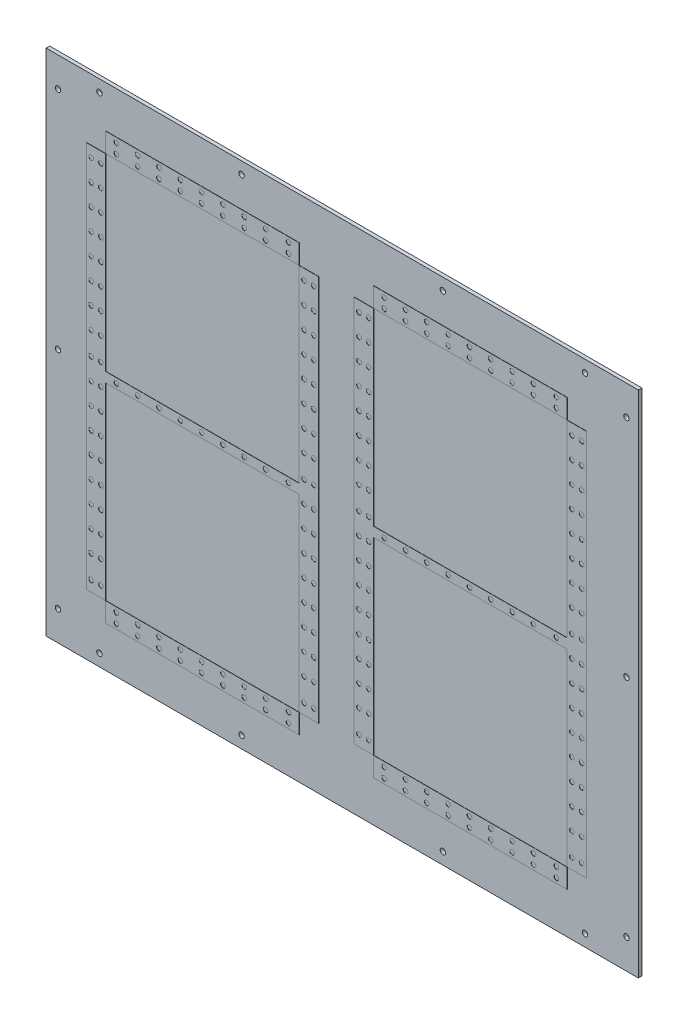
SolidWorks part; units mm, degrees
material "AISI 1020"
ref_plane "Front Plane" through (0, 0, 0) normal (0, 0, 1) x (1, 0, 0)
ref_plane "Top Plane" through (0, 0, 0) normal (0, 1, 0) x (1, 0, 0)
ref_plane "Right Plane" through (0, 0, 0) normal (1, 0, 0) x (0, 0, -1)
other "Caixa delimitadora"
ref_plane "Default Plane" through (-275, -250, -3) normal (0, 1, 0) x (1, 0, 0)
sketch "Esboço3" plane through (0, 0, 0) normal (0, 0, 1) x (1, 0, 0)
  line L0 (19.423, -163.6696) -> (49.423, -163.6696) construction
  line L2 (34.423, -163.6696) -> (34.423, -0.5317) construction
  line L5 (-0.277, -0.3121) -> (-0.277, 22.0323) construction
  line B0 (3.023, -171.9902) -> (-160.3346, -171.9902)
  line B1 (3.023, -4.4121) -> (-160.3346, -4.4121)
  line B2 (3.023, -0.3121) -> (3.023, 163.0455)
  line B3 (3.023, 3.7879) -> (-160.3346, 3.7879)
  line B4 (3.0164, 171.3782) -> (-160.3411, 171.3782)
  line B5 (11.223, -0.3121) -> (11.223, 163.0455)
  line B6 (3.023, -163.7902) -> (-160.3346, -163.7902)
  line B7 (3.0164, 163.1782) -> (-160.3411, 163.1782)
  line B8 (3.0164, 167.2782) -> (-160.3411, 167.2782) construction
  circle B9 centre (-5.9836, 167.2782) radius 2
  line B10 (3.0164, 163.1782) -> (3.0164, 171.3782)
  circle B11 centre (-43.3411, 167.2782) radius 2
  circle B12 centre (-151.3411, 167.2782) radius 2
  line B13 (-160.3411, 163.1782) -> (-160.3411, 171.3782)
  circle B14 centre (-61.3411, 167.2782) radius 2
  circle B15 centre (-25.3411, 167.2782) radius 2
  circle B16 centre (-79.3411, 167.2782) radius 2
  circle B17 centre (-97.3411, 167.2782) radius 2
  circle B18 centre (-115.3411, 167.2782) radius 2
  circle B19 centre (-133.3411, 167.2782) radius 2
  circle B20 centre (7.123, 154.0455) radius 2
  circle B21 centre (-5.977, -167.8902) radius 2
  line B22 (-160.3346, -171.9902) -> (-160.3346, -163.7902)
  line B23 (3.023, -171.9902) -> (3.023, -163.7902)
  circle B24 centre (-25.3346, -167.8902) radius 2
  circle B25 centre (-43.3346, -167.8902) radius 2
  circle B26 centre (-61.3346, -167.8902) radius 2
  circle B27 centre (-79.3346, -167.8902) radius 2
  circle B28 centre (-97.3346, -167.8902) radius 2
  circle B29 centre (-115.3346, -167.8902) radius 2
  circle B30 centre (-133.3346, -167.8902) radius 2
  circle B31 centre (-151.3346, -167.8902) radius 2
  circle B32 centre (-5.977, -0.3121) radius 2
  line B33 (-160.3346, -4.4121) -> (-160.3346, 3.7879)
  line B34 (3.023, -4.4121) -> (3.023, 3.7879)
  circle B35 centre (-25.3346, -0.3121) radius 2
  circle B36 centre (-43.3346, -0.3121) radius 2
  circle B37 centre (-61.3346, -0.3121) radius 2
  circle B38 centre (-79.3346, -0.3121) radius 2
  circle B39 centre (-97.3346, -0.3121) radius 2
  circle B40 centre (-115.3346, -0.3121) radius 2
  circle B41 centre (-133.3346, -0.3121) radius 2
  circle B42 centre (-151.3346, -0.3121) radius 2
  circle B43 centre (7.123, 8.6879) radius 2
  line B44 (3.023, 163.0455) -> (11.223, 163.0455)
  line B45 (3.023, -0.3121) -> (11.223, -0.3121)
  circle B46 centre (7.123, 28.0455) radius 2
  circle B47 centre (7.123, 46.0455) radius 2
  circle B48 centre (7.123, 64.0455) radius 2
  circle B49 centre (7.123, 82.0455) radius 2
  circle B50 centre (7.123, 100.0455) radius 2
  circle B51 centre (7.123, 118.0455) radius 2
  circle B52 centre (7.123, 136.0455) radius 2
  line B53 (3.023, -176.0902) -> (-160.3346, -176.0902) construction
  line B54 (3.023, -180.1902) -> (-160.3346, -180.1902)
  line B55 (3.023, -180.1902) -> (3.023, -171.9902)
  line B56 (3.023, -171.9902) -> (-160.3346, -171.9902)
  line B57 (-160.3346, -180.1902) -> (-160.3346, -171.9902)
  circle B58 centre (-5.977, -176.0902) radius 2
  circle B59 centre (-25.3346, -176.0902) radius 2
  circle B60 centre (-43.3346, -176.0902) radius 2
  circle B61 centre (-61.3346, -176.0902) radius 2
  circle B62 centre (-79.3346, -176.0902) radius 2
  circle B63 centre (-97.3346, -176.0902) radius 2
  circle B64 centre (-115.3346, -176.0902) radius 2
  circle B65 centre (-133.3346, -176.0902) radius 2
  circle B66 centre (-151.3346, -176.0902) radius 2
  line B67 (3.0164, 175.4782) -> (-160.3411, 175.4782) construction
  line B68 (3.0164, 171.3782) -> (-160.3411, 171.3782)
  line B69 (3.0164, 171.3782) -> (3.0164, 179.5782)
  line B70 (3.0164, 179.5782) -> (-160.3411, 179.5782)
  line B71 (-160.3411, 171.3782) -> (-160.3411, 179.5782)
  circle B72 centre (-5.9836, 175.4782) radius 2
  circle B73 centre (-25.3411, 175.4782) radius 2
  circle B74 centre (-43.3411, 175.4782) radius 2
  circle B75 centre (-61.3411, 175.4782) radius 2
  circle B76 centre (-79.3411, 175.4782) radius 2
  circle B77 centre (-97.3411, 175.4782) radius 2
  circle B78 centre (-115.3411, 175.4782) radius 2
  circle B79 centre (-133.3411, 175.4782) radius 2
  circle B80 centre (-151.3411, 175.4782) radius 2
  line B81 (11.223, -163.6696) -> (11.223, -0.3121)
  line B82 (3.023, -163.6696) -> (3.023, -0.3121)
  line B83 (7.123, -163.6696) -> (7.123, -0.3121) construction
  line B84 (3.023, -163.6696) -> (11.223, -163.6696)
  line B85 (3.023, -0.3121) -> (11.223, -0.3121)
  circle B86 centre (7.123, -154.6696) radius 2
  circle B87 centre (7.123, -135.3121) radius 2
  circle B88 centre (7.123, -117.3121) radius 2
  circle B89 centre (7.123, -99.3121) radius 2
  circle B90 centre (7.123, -81.3121) radius 2
  circle B91 centre (7.123, -63.3121) radius 2
  circle B92 centre (7.123, -45.3121) radius 2
  circle B93 centre (7.123, -27.3121) radius 2
  circle B94 centre (7.123, -9.3121) radius 2
  line B95 (-164.4346, -163.6696) -> (-164.4346, -0.3121) construction
  line B96 (-168.5346, -163.6696) -> (-168.5346, -0.3121)
  line B97 (-168.5346, -163.6696) -> (-160.3346, -163.6696)
  line B98 (-160.3346, -163.6696) -> (-160.3346, -0.3121)
  line B99 (-168.5346, -0.3121) -> (-160.3346, -0.3121)
  circle B100 centre (-164.4346, -154.6696) radius 2
  circle B101 centre (-164.4346, -135.3121) radius 2
  circle B102 centre (-164.4346, -117.3121) radius 2
  circle B103 centre (-164.4346, -99.3121) radius 2
  circle B104 centre (-164.4346, -81.3121) radius 2
  circle B105 centre (-164.4346, -63.3121) radius 2
  circle B106 centre (-164.4346, -45.3121) radius 2
  circle B107 centre (-164.4346, -27.3121) radius 2
  circle B108 centre (-164.4346, -9.3121) radius 2
  line B109 (-164.4346, -0.3121) -> (-164.4346, 163.0455) construction
  line B110 (-168.5346, -0.3121) -> (-168.5346, 163.0455)
  line B111 (-168.5346, -0.3121) -> (-160.3346, -0.3121)
  line B112 (-160.3346, -0.3121) -> (-160.3346, 163.0455)
  line B113 (-168.5346, 163.0455) -> (-160.3346, 163.0455)
  circle B114 centre (-164.4346, 8.6879) radius 2
  circle B115 centre (-164.4346, 28.0455) radius 2
  circle B116 centre (-164.4346, 46.0455) radius 2
  circle B117 centre (-164.4346, 64.0455) radius 2
  circle B118 centre (-164.4346, 82.0455) radius 2
  circle B119 centre (-164.4346, 100.0455) radius 2
  circle B120 centre (-164.4346, 118.0455) radius 2
  circle B121 centre (-164.4346, 136.0455) radius 2
  circle B122 centre (-164.4346, 154.0455) radius 2
  line B123 (15.323, -163.6696) -> (15.323, -0.3121) construction
  line B124 (11.223, -163.6696) -> (11.223, -0.3121)
  line B125 (11.223, -163.6696) -> (19.423, -163.6696)
  line B126 (19.423, -163.6696) -> (19.423, -0.3121)
  line B127 (11.223, -0.3121) -> (19.423, -0.3121)
  circle B128 centre (15.323, -154.6696) radius 2
  circle B129 centre (15.323, -135.3121) radius 2
  circle B130 centre (15.323, -117.3121) radius 2
  circle B131 centre (15.323, -99.3121) radius 2
  circle B132 centre (15.323, -81.3121) radius 2
  circle B133 centre (15.323, -63.3121) radius 2
  circle B134 centre (15.323, -45.3121) radius 2
  circle B135 centre (15.323, -27.3121) radius 2
  circle B136 centre (15.323, -9.3121) radius 2
  line B137 (11.223, -0.3121) -> (11.223, 163.0455)
  line B138 (11.223, -0.3121) -> (19.423, -0.3121)
  line B139 (19.423, -0.3121) -> (19.423, 163.0455)
  line B140 (11.223, 163.0455) -> (19.423, 163.0455)
  circle B141 centre (15.323, 8.6879) radius 2
  circle B142 centre (15.323, 28.0455) radius 2
  circle B143 centre (15.323, 46.0455) radius 2
  circle B144 centre (15.323, 64.0455) radius 2
  circle B145 centre (15.323, 82.0455) radius 2
  circle B146 centre (15.323, 100.0455) radius 2
  circle B147 centre (15.323, 118.0455) radius 2
  circle B148 centre (15.323, 136.0455) radius 2
  circle B149 centre (15.323, 154.0455) radius 2
  line B150 (-172.6346, -163.6696) -> (-172.6346, -0.3121) construction
  line B151 (-176.7346, -163.6696) -> (-176.7346, -0.3121)
  line B152 (-176.7346, -163.6696) -> (-168.5346, -163.6696)
  line B153 (-168.5346, -163.6696) -> (-168.5346, -0.3121)
  line B154 (-176.7346, -0.3121) -> (-168.5346, -0.3121)
  circle B155 centre (-172.6346, -154.6696) radius 2
  circle B156 centre (-172.6346, -135.3121) radius 2
  circle B157 centre (-172.6346, -117.3121) radius 2
  circle B158 centre (-172.6346, -99.3121) radius 2
  circle B159 centre (-172.6346, -81.3121) radius 2
  circle B160 centre (-172.6346, -63.3121) radius 2
  circle B161 centre (-172.6346, -45.3121) radius 2
  circle B162 centre (-172.6346, -27.3121) radius 2
  circle B163 centre (-172.6346, -9.3121) radius 2
  line B164 (-172.6346, -0.3121) -> (-172.6346, 163.0455) construction
  line B165 (-176.7346, -0.3121) -> (-176.7346, 163.0455)
  line B166 (-176.7346, -0.3121) -> (-168.5346, -0.3121)
  line B167 (-168.5346, -0.3121) -> (-168.5346, 163.0455)
  line B168 (-176.7346, 163.0455) -> (-168.5346, 163.0455)
  circle B169 centre (-172.6346, 8.6879) radius 2
  circle B170 centre (-172.6346, 28.0455) radius 2
  circle B171 centre (-172.6346, 46.0455) radius 2
  circle B172 centre (-172.6346, 64.0455) radius 2
  circle B173 centre (-172.6346, 82.0455) radius 2
  circle B174 centre (-172.6346, 100.0455) radius 2
  circle B175 centre (-172.6346, 118.0455) radius 2
  circle B176 centre (-172.6346, 136.0455) radius 2
  circle B177 centre (-172.6346, 154.0455) radius 2
  line B178 (229.1805, -171.9902) -> (65.823, -171.9902)
  line B179 (229.1805, -4.4121) -> (65.823, -4.4121)
  line B180 (229.1805, -0.3121) -> (229.1805, 163.0455)
  line B181 (229.1805, 3.7879) -> (65.823, 3.7879)
  line B182 (229.174, 171.3782) -> (65.8164, 171.3782)
  line B183 (237.3805, -0.3121) -> (237.3805, 163.0455)
  line B184 (229.1805, -163.7902) -> (65.823, -163.7902)
  line B185 (229.174, 163.1782) -> (65.8164, 163.1782)
  line B186 (229.174, 167.2782) -> (65.8164, 167.2782) construction
  circle B187 centre (220.174, 167.2782) radius 2
  line B188 (229.174, 163.1782) -> (229.174, 171.3782)
  circle B189 centre (182.8164, 167.2782) radius 2
  circle B190 centre (74.8164, 167.2782) radius 2
  line B191 (65.8164, 163.1782) -> (65.8164, 171.3782)
  circle B192 centre (164.8164, 167.2782) radius 2
  circle B193 centre (200.8164, 167.2782) radius 2
  circle B194 centre (146.8164, 167.2782) radius 2
  circle B195 centre (128.8164, 167.2782) radius 2
  circle B196 centre (110.8164, 167.2782) radius 2
  circle B197 centre (92.8164, 167.2782) radius 2
  circle B198 centre (233.2805, 154.0455) radius 2
  circle B199 centre (220.1805, -167.8902) radius 2
  line B200 (65.823, -171.9902) -> (65.823, -163.7902)
  line B201 (229.1805, -171.9902) -> (229.1805, -163.7902)
  circle B202 centre (200.823, -167.8902) radius 2
  circle B203 centre (182.823, -167.8902) radius 2
  circle B204 centre (164.823, -167.8902) radius 2
  circle B205 centre (146.823, -167.8902) radius 2
  circle B206 centre (128.823, -167.8902) radius 2
  circle B207 centre (110.823, -167.8902) radius 2
  circle B208 centre (92.823, -167.8902) radius 2
  circle B209 centre (74.823, -167.8902) radius 2
  circle B210 centre (220.1805, -0.3121) radius 2
  line B211 (65.823, -4.4121) -> (65.823, 3.7879)
  line B212 (229.1805, -4.4121) -> (229.1805, 3.7879)
  circle B213 centre (200.823, -0.3121) radius 2
  circle B214 centre (182.823, -0.3121) radius 2
  circle B215 centre (164.823, -0.3121) radius 2
  circle B216 centre (146.823, -0.3121) radius 2
  circle B217 centre (128.823, -0.3121) radius 2
  circle B218 centre (110.823, -0.3121) radius 2
  circle B219 centre (92.823, -0.3121) radius 2
  circle B220 centre (74.823, -0.3121) radius 2
  circle B221 centre (233.2805, 8.6879) radius 2
  line B222 (229.1805, 163.0455) -> (237.3805, 163.0455)
  line B223 (229.1805, -0.3121) -> (237.3805, -0.3121)
  circle B224 centre (233.2805, 28.0455) radius 2
  circle B225 centre (233.2805, 46.0455) radius 2
  circle B226 centre (233.2805, 64.0455) radius 2
  circle B227 centre (233.2805, 82.0455) radius 2
  circle B228 centre (233.2805, 100.0455) radius 2
  circle B229 centre (233.2805, 118.0455) radius 2
  circle B230 centre (233.2805, 136.0455) radius 2
  line B231 (229.1805, -0.3121) -> (65.823, -0.3121) construction
  line B232 (233.2805, -0.3121) -> (233.2805, 163.0455) construction
  line B233 (229.1805, -180.1902) -> (65.823, -180.1902)
  line B234 (229.1805, -180.1902) -> (229.1805, -171.9902)
  line B235 (229.1805, -171.9902) -> (65.823, -171.9902)
  line B236 (65.823, -180.1902) -> (65.823, -171.9902)
  circle B237 centre (220.1805, -176.0902) radius 2
  circle B238 centre (200.823, -176.0902) radius 2
  circle B239 centre (182.823, -176.0902) radius 2
  circle B240 centre (164.823, -176.0902) radius 2
  circle B241 centre (146.823, -176.0902) radius 2
  circle B242 centre (128.823, -176.0902) radius 2
  circle B243 centre (110.823, -176.0902) radius 2
  circle B244 centre (92.823, -176.0902) radius 2
  circle B245 centre (74.823, -176.0902) radius 2
  line B246 (229.174, 175.4782) -> (65.8164, 175.4782) construction
  line B247 (229.174, 171.3782) -> (65.8164, 171.3782)
  line B248 (229.174, 171.3782) -> (229.174, 179.5782)
  line B249 (229.174, 179.5782) -> (65.8164, 179.5782)
  line B250 (65.8164, 171.3782) -> (65.8164, 179.5782)
  circle B251 centre (220.174, 175.4782) radius 2
  circle B252 centre (200.8164, 175.4782) radius 2
  circle B253 centre (182.8164, 175.4782) radius 2
  circle B254 centre (164.8164, 175.4782) radius 2
  circle B255 centre (146.8164, 175.4782) radius 2
  circle B256 centre (128.8164, 175.4782) radius 2
  circle B257 centre (110.8164, 175.4782) radius 2
  circle B258 centre (92.8164, 175.4782) radius 2
  circle B259 centre (74.8164, 175.4782) radius 2
  line B260 (237.3805, -163.6696) -> (237.3805, -0.3121)
  line B261 (229.1805, -163.6696) -> (229.1805, -0.3121)
  line B262 (233.2805, -163.6696) -> (233.2805, -0.3121) construction
  line B263 (229.1805, -163.6696) -> (237.3805, -163.6696)
  line B264 (229.1805, -0.3121) -> (237.3805, -0.3121)
  circle B265 centre (233.2805, -154.6696) radius 2
  circle B266 centre (233.2805, -135.3121) radius 2
  circle B267 centre (233.2805, -117.3121) radius 2
  circle B268 centre (233.2805, -99.3121) radius 2
  circle B269 centre (233.2805, -81.3121) radius 2
  circle B270 centre (233.2805, -63.3121) radius 2
  circle B271 centre (233.2805, -45.3121) radius 2
  circle B272 centre (233.2805, -27.3121) radius 2
  circle B273 centre (233.2805, -9.3121) radius 2
  line B274 (57.623, -163.6696) -> (57.623, -0.3121)
  line B275 (57.623, -163.6696) -> (65.823, -163.6696)
  line B276 (65.823, -163.6696) -> (65.823, -0.3121)
  line B277 (57.623, -0.3121) -> (65.823, -0.3121)
  circle B278 centre (61.723, -154.6696) radius 2
  circle B279 centre (61.723, -135.3121) radius 2
  circle B280 centre (61.723, -117.3121) radius 2
  circle B281 centre (61.723, -99.3121) radius 2
  circle B282 centre (61.723, -81.3121) radius 2
  circle B283 centre (61.723, -63.3121) radius 2
  circle B284 centre (61.723, -45.3121) radius 2
  circle B285 centre (61.723, -27.3121) radius 2
  circle B286 centre (61.723, -9.3121) radius 2
  line B287 (57.623, -0.3121) -> (57.623, 163.0455)
  line B288 (57.623, -0.3121) -> (65.823, -0.3121)
  line B289 (65.823, -0.3121) -> (65.823, 163.0455)
  line B290 (57.623, 163.0455) -> (65.823, 163.0455)
  circle B291 centre (61.723, 8.6879) radius 2
  circle B292 centre (61.723, 28.0455) radius 2
  circle B293 centre (61.723, 46.0455) radius 2
  circle B294 centre (61.723, 64.0455) radius 2
  circle B295 centre (61.723, 82.0455) radius 2
  circle B296 centre (61.723, 100.0455) radius 2
  circle B297 centre (61.723, 118.0455) radius 2
  circle B298 centre (61.723, 136.0455) radius 2
  circle B299 centre (61.723, 154.0455) radius 2
  line B300 (241.4805, -163.6696) -> (241.4805, -0.3121) construction
  line B301 (237.3805, -163.6696) -> (237.3805, -0.3121)
  line B302 (237.3805, -163.6696) -> (245.5805, -163.6696)
  line B303 (245.5805, -163.6696) -> (245.5805, -0.3121)
  line B304 (237.3805, -0.3121) -> (245.5805, -0.3121)
  circle B305 centre (241.4805, -154.6696) radius 2
  circle B306 centre (241.4805, -135.3121) radius 2
  circle B307 centre (241.4805, -117.3121) radius 2
  circle B308 centre (241.4805, -99.3121) radius 2
  circle B309 centre (241.4805, -81.3121) radius 2
  circle B310 centre (241.4805, -63.3121) radius 2
  circle B311 centre (241.4805, -45.3121) radius 2
  circle B312 centre (241.4805, -27.3121) radius 2
  circle B313 centre (241.4805, -9.3121) radius 2
  line B314 (237.3805, -0.3121) -> (237.3805, 163.0455)
  line B315 (237.3805, -0.3121) -> (245.5805, -0.3121)
  line B316 (245.5805, -0.3121) -> (245.5805, 163.0455)
  line B317 (237.3805, 163.0455) -> (245.5805, 163.0455)
  circle B318 centre (241.4805, 8.6879) radius 2
  circle B319 centre (241.4805, 28.0455) radius 2
  circle B320 centre (241.4805, 46.0455) radius 2
  circle B321 centre (241.4805, 64.0455) radius 2
  circle B322 centre (241.4805, 82.0455) radius 2
  circle B323 centre (241.4805, 100.0455) radius 2
  circle B324 centre (241.4805, 118.0455) radius 2
  circle B325 centre (241.4805, 136.0455) radius 2
  circle B326 centre (241.4805, 154.0455) radius 2
  line B327 (53.523, -163.6696) -> (53.523, -0.3121) construction
  line B328 (49.423, -163.6696) -> (49.423, -0.3121)
  line B329 (49.423, -163.6696) -> (57.623, -163.6696)
  line B330 (57.623, -163.6696) -> (57.623, -0.3121)
  line B331 (49.423, -0.3121) -> (57.623, -0.3121)
  circle B332 centre (53.523, -154.6696) radius 2
  circle B333 centre (53.523, -135.3121) radius 2
  circle B334 centre (53.523, -117.3121) radius 2
  circle B335 centre (53.523, -99.3121) radius 2
  circle B336 centre (53.523, -81.3121) radius 2
  circle B337 centre (53.523, -63.3121) radius 2
  circle B338 centre (53.523, -45.3121) radius 2
  circle B339 centre (53.523, -27.3121) radius 2
  circle B340 centre (53.523, -9.3121) radius 2
  line B341 (53.523, -0.3121) -> (53.523, 163.0455) construction
  line B342 (49.423, -0.3121) -> (49.423, 163.0455)
  line B343 (49.423, -0.3121) -> (57.623, -0.3121)
  line B344 (57.623, -0.3121) -> (57.623, 163.0455)
  line B345 (49.423, 163.0455) -> (57.623, 163.0455)
  circle B346 centre (53.523, 8.6879) radius 2
  circle B347 centre (53.523, 28.0455) radius 2
  circle B348 centre (53.523, 46.0455) radius 2
  circle B349 centre (53.523, 64.0455) radius 2
  circle B350 centre (53.523, 82.0455) radius 2
  circle B351 centre (53.523, 100.0455) radius 2
  circle B352 centre (53.523, 118.0455) radius 2
  circle B353 centre (53.523, 136.0455) radius 2
  circle B354 centre (53.523, 154.0455) radius 2
  dimension "D1" = 30
sketch_block_instance "Bloco5-1"
sketch_block "Bloco5"
sketch_block_instance "Bloco4-2"
sketch_block "Bloco4" parameters "D1"=9, "D2"=9
sketch_block_instance "Bloco4-4"
sketch_block_instance "Bloco4-5"
sketch_block_instance "Bloco4-7"
sketch_block_instance "Bloco4-12"
sketch_block_instance "Bloco4-13"
sketch_block_instance "Bloco4-20"
sketch_block_instance "Bloco4-21"
sketch_block_instance "Bloco4-22"
sketch_block_instance "Bloco4-23"
sketch_block_instance "Bloco4-24"
sketch_block_instance "Bloco4-25"
sketch_block_instance "Bloco4-26"
sketch_block_instance "Bloco5-2" parameters "D1"=12.9798, "D2"=27.8767, "D6"=4, "D3"=4, "D4"=31.6483, "D5"=38.1471, "D7"=9, "D8"=9
sketch "Esboço4" plane through (0, 0, 0) normal (0, 0, 1) x (1, 0, 0)
  line L0 (39.1575, 215) -> (39.1575, -215) construction
  line L2 (-210.8425, 215) -> (-210.8425, -215)
  line L4 (289.1575, 215) -> (289.1575, -215)
  line L15 (-210.8425, -215) -> (289.1575, -215)
  line L17 (-210.8425, 215) -> (289.1575, 215)
  dimension "D3" = 500
  dimension "D4" = 430
base flange "Flange-base1" sketch "Esboço4" thickness 3 reverse thickness direction no parameters "D1"=0.7366
extrude "Ressalto-extrusão1" add sketch "Esboço3" along normal blind 0.2
sketch "Esboço13" plane through (0, 0, 0) normal (0, 0, 1) x (1, 0, 0)
  line L0 (-210.8425, 215) -> (289.1575, 215) construction
  line L1 (-210.8425, 215) -> (-210.8425, -215) construction
  line L2 (39.1575, 0) -> (39.1575, 6.2685) construction
  line L3 (39.1575, 215) -> (39.1575, -215) construction
  line L4 (39.1575, 0) -> (-10.5668, 0) construction
  line L7 (-200.8425, 205) -> (279.1575, 205) construction
  line L8 (-200.8425, 205) -> (-200.8425, -205) construction
  line L9 (-200.8425, -205) -> (279.1575, -205) construction
  line L10 (279.1575, 205) -> (279.1575, -205) construction
  circle A0 centre (-165.8425, 205) radius 2.3
  circle A1 centre (-200.8425, 190) radius 2.3
  circle A2 centre (-45.8425, 205) radius 2.3
  circle A4 centre (124.1575, 205) radius 2.3
  circle A5 centre (244.1575, 205) radius 2.3
  circle A6 centre (279.1575, 190) radius 2.3
  circle A7 centre (279.1575, -190) radius 2.3
  circle A8 centre (244.1575, -205) radius 2.3
  circle A9 centre (124.1575, -205) radius 2.3
  circle A10 centre (-45.8425, -205) radius 2.3
  circle A11 centre (-200.8425, -190) radius 2.3
  circle A12 centre (-165.8425, -205) radius 2.3
  circle A13 centre (240, 0) radius 2.3
  circle A14 centre (-200.8425, -0.3121) radius 2.3
  circle A15 centre (279.1575, 0) radius 2.3
  dimension "D1" = 10
  dimension "D2" = 45
  dimension "D4" = 10
  dimension "D5" = 120
  dimension "D6" = 4.6
  dimension "D7" = 410
extrude "Corte-extrusão3" cut sketch "Esboço13" against normal blind 3
sketch "Curva-Linhas1" [suppressed] plane through (0, 0, 0) normal (0, 1, 0) x (1, 0, 0)
sketch "Caixa delimitadora1" [suppressed] plane through (0, 0, 0) normal (0, 1, 0) x (1, 0, 0)
sheet metal parameters "Chapa metálica1" thickness 3 parameters "D1"=0.7366
flat pattern "Padrão-Plano10" [suppressed]
sketch "Esboço10" plane through (0, 0, 0) normal (0, 1, 0) x (1, 0, 0)
sketch "Esboço11" [suppressed] plane through (0, 0, 0) normal (0, 1, 0) x (1, 0, 0)
sheet metal parameters "Chapa metálica2" thickness 3 parameters "D1"=0.7366
flat pattern "Padrão-Plano9"
sketch "Curva-Linhas3" plane through (0, 0, 0) normal (0, 1, 0) x (1, 0, 0)
sketch "Caixa delimitadora3" [suppressed] plane through (0, 0, 0) normal (0, 1, 0) x (1, 0, 0)
sheet metal parameters "Chapa metálica12" thickness 3 parameters "D1"=0.7366
flat pattern "Padrão-Plano10"
sketch "Esboço10" plane through (0, 0, 0) normal (0, 1, 0) x (1, 0, 0)
sketch "Esboço11" [suppressed] plane through (0, 0, 0) normal (0, 1, 0) x (1, 0, 0)
sheet metal parameters "Chapa metálica15" thickness 3 parameters "D1"=0.7366
flat pattern "Padrão-Plano10"
sketch "Esboço10" plane through (0, 0, 0) normal (0, 1, 0) x (1, 0, 0)
sketch "Esboço11" [suppressed] plane through (0, 0, 0) normal (0, 1, 0) x (1, 0, 0)
